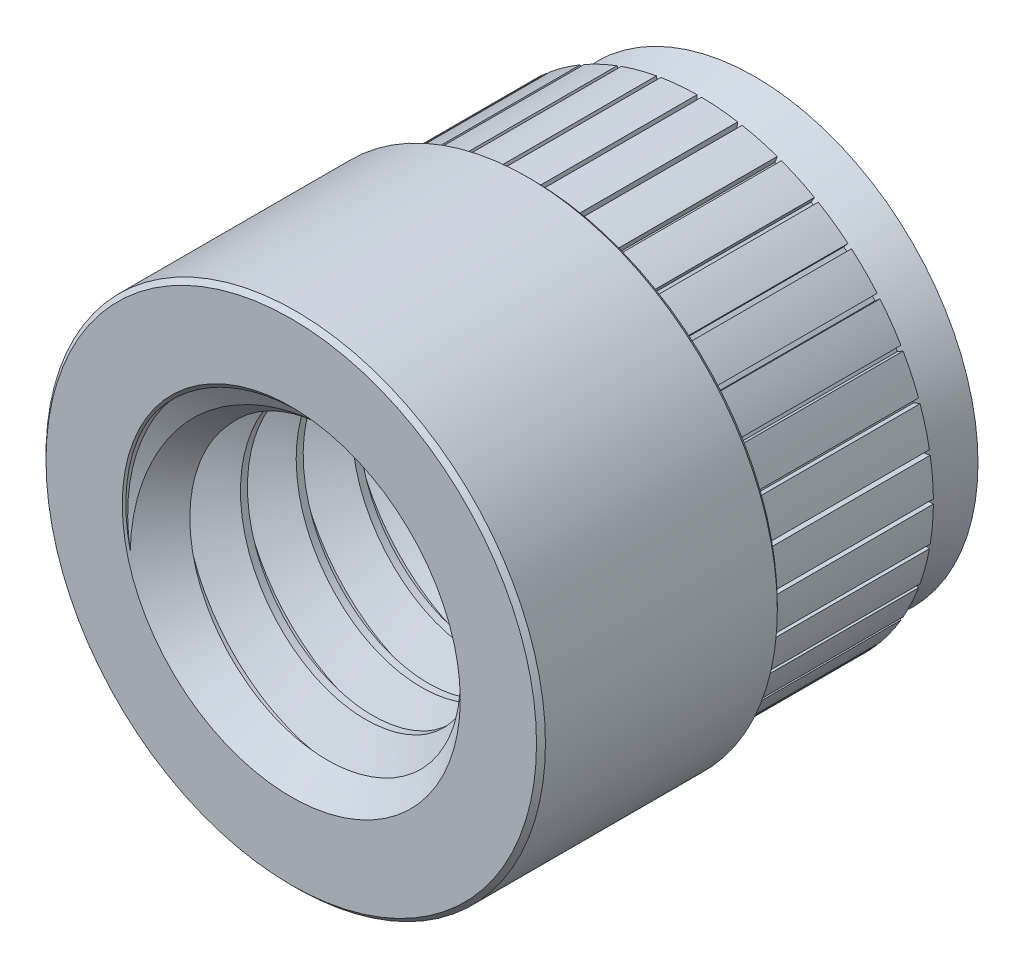
SolidWorks part; units mm, degrees
ref_plane "Front Plane" through (0, 0, 0) normal (0, 0, 1) x (1, 0, 0)
ref_plane "Top Plane" through (0, 0, 0) normal (0, 1, 0) x (1, 0, 0)
ref_plane "Right Plane" through (0, 0, 0) normal (1, 0, 0) x (0, 0, -1)
sketch "Sketch1" plane through (0, 0, 0) normal (0, 0, 1) x (1, 0, 0)
  circle A0 centre (0, 0) radius 7.112
  dimension "A" = 14.224
extrude "Extrude1" add sketch "Sketch1" against normal blind 6.858
sketch "Sketch15" plane through (0, 0, -6.858) normal (0, 0, -1) x (-1, 0, 0)
  circle A0 centre (0, 0) radius 6.35
  dimension "hole dia" = 12.7
sketch "Sketch2" plane through (0, 0, -6.858) normal (0, 0, -1) x (-1, 0, 0)
  circle A0 centre (0, 0) radius 6.6675
  dimension "D1" = 13.335
extrude "Extrude2" add sketch "Sketch2" along normal blind 6.35
sketch "Sketch3" plane through (0, 0, -13.208) normal (0, 0, -1) x (-1, 0, 0)
  line L0 (0, 6.477) -> (0, 7.112)
  circle A1 centre (0, 0) radius 7.112 construction
  circle A2 centre (0, 0) radius 6.477
  circle A3 centre (0, 0) radius 6.477 construction
  dimension "D1" = 0.1905
extrude "Cut-Extrude-Thin1" cut sketch "Sketch3" against normal up to surface (6.35 mm away) thin up to face at (7.112, 0, -6.858) thin type mid plane wall 0.127
pattern_circular "CirPattern1" count 36 over 360 about axis through (0, 0, 0) along (0, 0, 1) of "Cut-Extrude-Thin1"
sketch "Sketch5" plane through (0, 0, -13.208) normal (0, 0, -1) x (-1, 0, 0)
  circle A0 centre (0, 0) radius 7.112 construction
  circle A3 centre (0, 0) radius 6.35
  dimension "C" = 12.7
extrude "Cut-Extrude1" cut sketch "Sketch5" against normal blind 1.5875 draft 20 flip side to cut draft outward yes
chamfer "Chamfer2" distance 0.127 angle 45 2 edges at (7.112, 0, 0) (7.112, 0, -6.858)
sketch "Sketch7" plane through (0, 0, 0) normal (0, 0, 1) x (1, 0, 0)
  circle A0 centre (0, 0) radius 4.7625
  dimension "Thread Od" = 9.525
extrude "Cut-Extrude3" cut sketch "Sketch7" against normal through all
sketch "Sketch8" plane through (0, 0, -13.208) normal (0, 0, -1) x (-1, 0, 0)
  circle A0 centre (0, 0) radius 4.7625 construction
  circle A1 centre (0, 0) radius 4.7625
curve "Helix/Spiral1" pitch 1.5875 height 16.383 turns 10.32 parameters "pitch"=1.5875
sketch "Sketch9" plane through (0, 0, 0) normal (1, 0, 0) x (0, 0, -1)
  line L0 (14.5971, 4.7625) -> (14.0017, 3.7314)
  line L1 (14.0017, 3.7314) -> (13.8033, 3.7314)
  line L2 (13.8033, 3.7314) -> (13.208, 4.7625)
  line L3 (14.5971, 4.7625) -> (13.208, 4.7625)
  line L4 (13.9025, 4.7625) -> (13.9025, 3.7314) construction
  line L5 (14.2994, 4.2469) -> (13.5057, 4.2469) construction
  line L6 (13.208, -4.7625) -> (13.208, 4.7625) construction
  dimension "D1" = 60
  dimension "D2" = 0.1984
  dimension "D3" = 0.7937
sweep "Sweep1" add profiles "Sketch9" path "Helix/Spiral1"
sketch "Sketch10" plane through (0, 0, 0) normal (0, 0, 1) x (1, 0, 0)
  circle A0 centre (0, 0) radius 7.112 construction
  circle A1 centre (0, 0) radius 7.112
extrude "Cut-Extrude4" cut sketch "Sketch10" along normal through all
sketch "Sketch11" plane through (0, 0, -13.208) normal (0, 0, -1) x (-1, 0, 0)
  circle A1 centre (0, 0) radius 6.35 construction
  circle A2 centre (0, 0) radius 6.35
extrude "Cut-Extrude5" cut sketch "Sketch11" along normal through all
sketch "Sketch13" plane through (0, 0, 0) normal (0, 0, 1) x (1, 0, 0)
  circle A2 centre (0, 0) radius 4.8133
  circle A3 centre (0, 0) radius 4.8133
  dimension "D1" = 0.0508
extrude "Cut-Extrude6" cut sketch "Sketch13" against normal through all draft 45
sketch "Sketch14" plane through (0, 0, -13.208) normal (0, 0, -1) x (-1, 0, 0)
  circle A2 centre (0, 0) radius 4.8133
  circle A3 centre (0, 0) radius 4.8133
  dimension "D1" = 0.0508
extrude "Cut-Extrude7" cut sketch "Sketch14" against normal through all draft 45
equation "\"D3@Helix/Spiral1\" = \"B@Extrude1\"+\"panel min.@Extrude2\"+.125"
equation "\"D2@Sketch9\" = \"pitch@Helix/Spiral1\"*.125"
equation "\"D3@Sketch9\" = \"pitch@Helix/Spiral1\"*.50"
equation "\"D1@Sketch2\" = \"hole dia@Sketch15\"+.025"
equation "\"D1@Cut-Extrude1\" = \"panel min.@Extrude2\"*.25"
